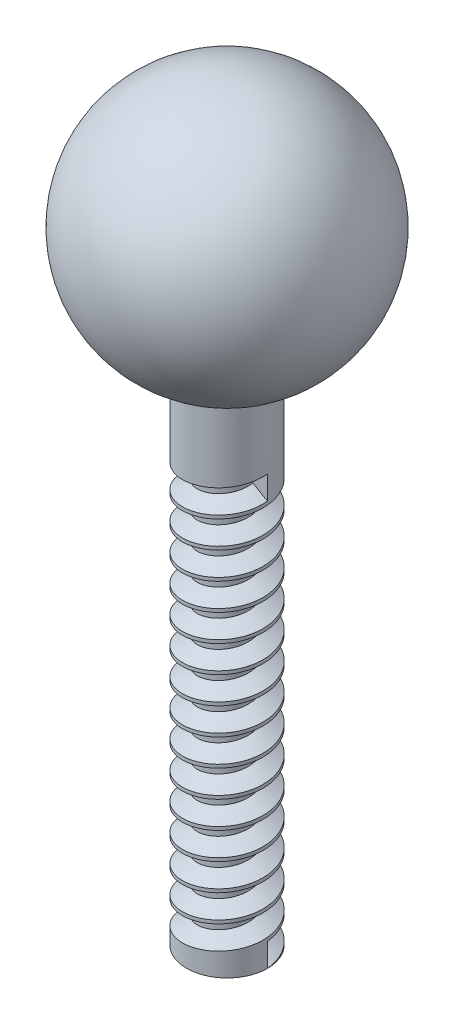
SolidWorks part; units mm, degrees
material "Plain Carbon Steel"
ref_plane "Front Plane" through (0, 0, 0) normal (0, 0, 1) x (1, 0, 0)
ref_plane "Top Plane" through (0, 0, 0) normal (0, 1, 0) x (1, 0, 0)
ref_plane "Right Plane" through (0, 0, 0) normal (1, 0, 0) x (0, 0, -1)
sketch "Sketch1" plane through (0, 0, 0) normal (0, 1, 0) x (1, 0, 0)
  line L0 (0, 9.5) -> (0, -9.5)
  circle A0 centre (0, 0) radius 9.5
  dimension "D1" = 19
revolve "Revolve1" add sketch "Sketch1" angle 360 about L0 region at (4.0319, 0, 0)
sketch "Sketch12" plane through (0, 0, 0) normal (0, 0, 1) x (1, 0, 0)
  line L0 (0, 0) -> (0, -46.0957)
  line L1 (0, -46.0957) -> (3, -46.0957)
  line L2 (3, 0) -> (3, -46.0957)
  line L3 (0, 0) -> (0, -33.3448) construction
  line L4 (3, 0) -> (3, -33.3448) construction
  line L5 (0, 0) -> (3, 0)
  dimension "D2" = 3
revolve "Revolve2" add sketch "Sketch12" angle 360 about L0
thread "Thread2" pitch 2 method cut profile "Thread Profile2" start angle 0, offset 0, length 30, pitch 2, diameter 6
ref_plane "Plane2" through (3, -46.0957, 0) normal (0, 0, 1) x (1, 0, 0)
sketch "Thread Profile2" plane through (3, -46.0957, 0) normal (0, 0, 1) x (1, 0, 0)
  line L0 (0, 0) -> (0, 2) construction
  line L11 (0, 0) -> (0, 1.75)
  line L12 (0, 1.75) -> (-1.0825, 1.125)
  line L13 (-1.0825, 1.125) -> (-1.0825, 0.625)
  line L15 (-1.0825, 0.625) -> (0, 0)
  line L17 (-1.0825, 0.875) -> (0, 0.875) construction
  point P2 (0, 0)
  dimension "Pitch" = 2
  dimension "Profile_Angle" = 60
  dimension "Profile_Land" = 0.5
  dimension "Profile_Height" = 1.0825
